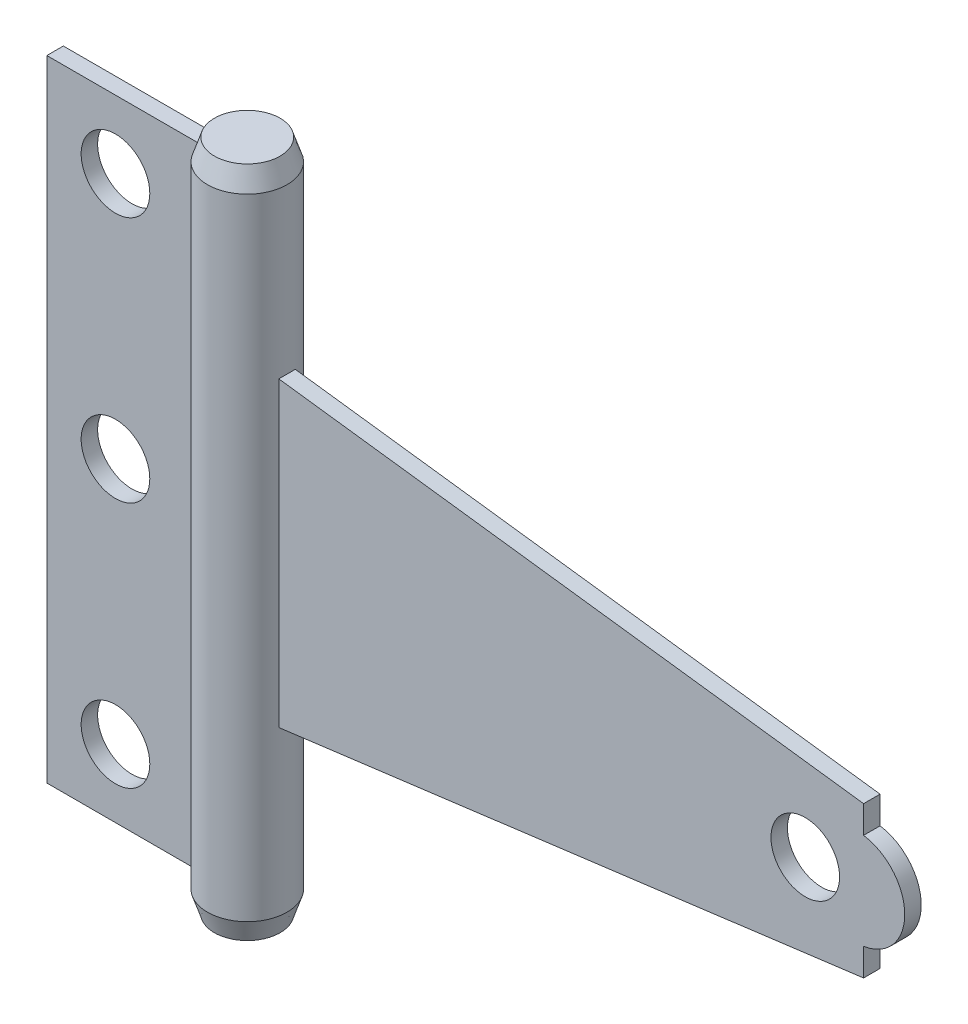
SolidWorks part; units mm, degrees
ref_plane "Front Plane" through (0, 0, 0) normal (0, 0, 1) x (1, 0, 0)
ref_plane "Top Plane" through (0, 0, 0) normal (0, 1, 0) x (1, 0, 0)
ref_plane "Right Plane" through (0, 0, 0) normal (1, 0, 0) x (0, 0, -1)
sketch "Sketch1" plane through (0, 0, 0) normal (0, 0, 1) x (1, 0, 0)
  line L0 (0, 0) -> (0, 75.232) construction
  line L1 (2.394, 24.5) -> (-2.394, 24.5)
  line L2 (-2.9, 22.95) -> (-2.394, 24.5)
  line L3 (-2.9, 22.95) -> (-14, 22.95)
  line L4 (-14, 22.95) -> (-14, -22.95)
  line L5 (2.394, 24.5) -> (2.9, 22.95)
  line L6 (2.9, 22.95) -> (2.9, 11)
  line L7 (2.9, 11) -> (45.5, 5.5)
  line L8 (45.5, 5.5) -> (45.5, 3.5)
  line L9 (0, 0) -> (133.1524, 0) construction
  line L10 (-2.9, 22.95) -> (-2.9, -22.95)
  line L11 (2.9, 11) -> (2.9, -11)
  line L12 (45.5, -5.5) -> (45.5, -3.5)
  line L13 (2.9, -11) -> (45.5, -5.5)
  line L14 (2.9, -22.95) -> (2.9, -11)
  line L15 (2.394, -24.5) -> (2.9, -22.95)
  line L16 (-2.9, -22.95) -> (-14, -22.95)
  line L17 (-2.9, -22.95) -> (-2.394, -24.5)
  line L18 (2.394, -24.5) -> (-2.394, -24.5)
  line L19 (0, 24.5) -> (0, -24.5)
  arc A0 (45.5, 3.5) -> (45.5, -3.5) centre (44.9583, 0) cw
  circle A1 centre (-9, 18) radius 2.5
  circle A2 centre (-9, 0) radius 2.5
  circle A3 centre (-9, -18) radius 2.5
  circle A4 centre (41.25, 0) radius 2.5
  point P5 (48.5, 0)
  point P18 (2.9, 0)
  point P19 (-2.9, 0)
  point P23 (-14, 0)
  dimension "D8" = 5
  dimension "D9" = 5
  dimension "D10" = 23
  dimension "D11" = 23
  dimension "D14" = 5
  dimension "D1" = 14
  dimension "D2" = 5.8
  dimension "D3" = 49
  dimension "D4" = 45.9
  dimension "D5" = 22
  dimension "D6" = 11
  dimension "D7" = 48.5
  dimension "D12" = 45.5
  dimension "D13" = 4.25
  dimension "D15" = 2
extrude "Boss-Extrude1" add sketch "Sketch1" along normal mid plane 1.2 contours L16 L10 L3 L4 | A0 L8 L7 L11 L13 L12 region at (21.8542, 0, 0) region at (-3.3722, 0, 0)
revolve "Revolve1" add sketch "Sketch1<5>" angle 360 about L0 region at (1.4429, 0, 0)
sketch "Sketch1<5>" plane through (0, 0, 0) normal (0, 0, 1) x (1, 0, 0) same geometry as "Sketch1"
ref_plane "Plane1" through (0, 0, 2.3) normal (0, 0, 1) x (1, 0, 0)
sketch "Sketch2" plane through (0, 0, 2.3) normal (0, 0, 1) x (1, 0, 0)
  line L0 (0, 0) -> (0, 75.232) construction
  line L1 (0, 0) -> (0, 75.232) construction
  line L2 (2.394, -24.5) -> (-2.394, -24.5) construction
  line L3 (2.394, -24.5) -> (2.9, -22.95) construction
  line L4 (2.9, -22.95) -> (2.9, -11) construction
  line L5 (2.9, 11) -> (2.9, -11) construction
  line L6 (2.9, 22.95) -> (2.9, 11) construction
  line L7 (2.394, 24.5) -> (2.9, 22.95) construction
  line L8 (0, 24.5) -> (0, -24.5) construction
  line L9 (2.394, 24.5) -> (-2.394, 24.5) construction
  line L10 (2.394, -24.5) -> (0, -24.5)
  line L11 (2.394, -24.5) -> (2.9, -22.95)
  line L12 (2.9, -22.95) -> (2.9, -11)
  line L13 (2.9, 11) -> (2.9, -11)
  line L14 (2.9, 22.95) -> (2.9, 11)
  line L15 (2.394, 24.5) -> (2.9, 22.95)
  line L16 (0, 24.5) -> (0, -24.5)
  line L17 (2.394, 24.5) -> (0, 24.5)
equation "\"A\"= 5.8mm / 2 - 0.6mm"
equation "\"D1@Plane1\"=\"A\""
